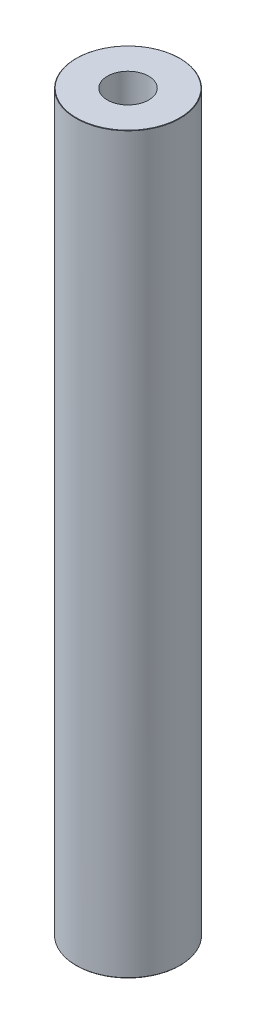
SolidWorks part; units mm, degrees
ref_plane "Front Plane" through (0, 0, 0) normal (0, 0, 1) x (1, 0, 0)
ref_plane "Top Plane" through (0, 0, 0) normal (0, 1, 0) x (1, 0, 0)
ref_plane "Right Plane" through (0, 0, 0) normal (1, 0, 0) x (0, 0, -1)
sketch "Sketch1" plane through (0, 0, 0) normal (0, 1, 0) x (1, 0, 0)
  circle A0 centre (0, 0) radius 42.5
  dimension "SHAFT_OD" = 85
extrude "Boss-Extrude1" add sketch "Sketch1" along normal blind 600
sketch "Sketch2" plane through (0, 0, 0) normal (0, 1, 0) x (1, 0, 0)
  circle A0 centre (0, 0) radius 16.9059
  dimension "BORE_D" = 33.8118
extrude "Cut-Extrude1" cut sketch "Sketch2" along normal through all
chamfer "Chamfer1" distance 0.2242 angle 56.518 2 edges at (0, 600, 42.5) (0, 0, 42.5) first distance on face at (0, 600, 42.5) first distance on face at (0, 0, 16.9059)
